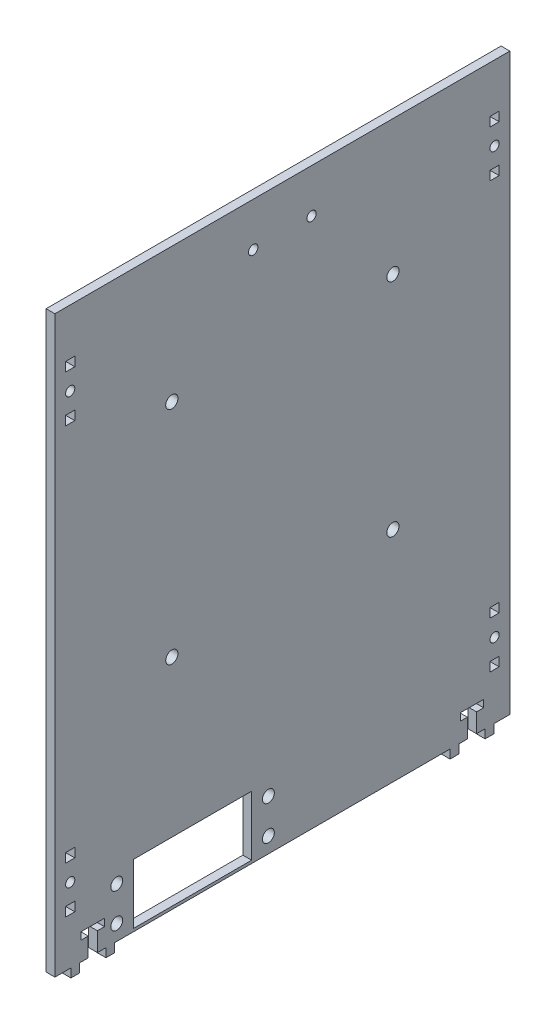
SolidWorks part; units mm, degrees
ref_plane "Front Plane" through (0, 0, 0) normal (0, 0, 1) x (1, 0, 0)
ref_plane "Top Plane" through (0, 0, 0) normal (0, 1, 0) x (1, 0, 0)
ref_plane "Right Plane" through (0, 0, 0) normal (1, 0, 0) x (0, 0, -1)
sketch "Sketch1" plane through (0, 0, 0) normal (1, 0, 0) x (0, 0, -1)
  line L0 (11.425, 0) -> (8.5, 0)
  line L1 (135.5, -3) -> (135.5, 0)
  line L2 (67.45, 21.5) -> (26.95, 21.5)
  line L3 (26.95, 21.5) -> (26.95, 1)
  line L4 (67.45, 21.5) -> (67.45, 1)
  line L5 (26.95, 1) -> (67.45, 1)
  line L6 (8.5, 0) -> (8.5, -3)
  line L7 (8.5, -3) -> (5.5, -3)
  line L8 (0, 0) -> (0, 197)
  line L9 (5.5, -3) -> (5.5, 0)
  line L10 (11.425, 0) -> (11.425, 6.5)
  line L11 (11.425, 6.5) -> (9, 6.5)
  line L12 (9, 6.5) -> (9, 9)
  line L13 (9, 9) -> (17, 9)
  line L14 (17, 9) -> (17, 6.5)
  line L15 (17, 6.5) -> (14.575, 6.5)
  line L16 (14.575, 6.5) -> (14.575, 0)
  line L17 (-1000, 98.5) -> (49000, 98.5) construction
  line L18 (3.675, 16) -> (6.825, 16)
  line L19 (3.675, 16) -> (3.675, 19.15)
  line L20 (3.675, 19.15) -> (6.825, 19.15)
  line L21 (6.825, 16) -> (6.825, 19.15)
  line L22 (3.675, 16) -> (6.825, 19.15) construction
  line L23 (3.675, 19.15) -> (6.825, 16) construction
  line L24 (3.675, 32) -> (6.825, 32)
  line L25 (3.675, 32) -> (3.675, 35.15)
  line L26 (3.675, 35.15) -> (6.825, 35.15)
  line L27 (6.825, 32) -> (6.825, 35.15)
  line L28 (3.675, 32) -> (6.825, 35.15) construction
  line L29 (3.675, 35.15) -> (6.825, 32) construction
  line L30 (14.575, 0) -> (17.5, 0)
  line L31 (78, -1000) -> (78, 49000) construction
  line L32 (3.675, 161.85) -> (6.825, 165) construction
  line L33 (3.675, 165) -> (6.825, 161.85) construction
  line L34 (3.675, 177.85) -> (6.825, 181) construction
  line L35 (3.675, 181) -> (6.825, 177.85) construction
  line L36 (0, 197) -> (156, 197)
  line L37 (6.825, 165) -> (6.825, 161.85)
  line L38 (3.675, 161.85) -> (6.825, 161.85)
  line L39 (3.675, 165) -> (3.675, 161.85)
  line L40 (3.675, 165) -> (6.825, 165)
  line L41 (6.825, 181) -> (6.825, 177.85)
  line L42 (3.675, 177.85) -> (6.825, 177.85)
  line L43 (3.675, 181) -> (3.675, 177.85)
  line L44 (3.675, 181) -> (6.825, 181)
  line L45 (5.5, 0) -> (0, 0)
  line L46 (17.5, 0) -> (17.5, -3)
  line L47 (17.5, -3) -> (20.5, -3)
  line L48 (20.5, -3) -> (20.5, 0)
  line L49 (20.5, 0) -> (135.5, 0)
  line L50 (138.5, -3) -> (135.5, -3)
  line L51 (138.5, 0) -> (138.5, -3)
  line L52 (141.425, 0) -> (138.5, 0)
  line L53 (144.575, 0) -> (147.5, 0)
  line L54 (150.5, 0) -> (156, 0)
  line L55 (150.5, -3) -> (150.5, 0)
  line L56 (147.5, -3) -> (150.5, -3)
  line L57 (147.5, 0) -> (147.5, -3)
  line L58 (37, 71.9) -> (37, 153.9) construction
  line L59 (37, 153.9) -> (119, 153.9) construction
  line L60 (119, 153.9) -> (119, 71.9) construction
  line L61 (152.325, 181) -> (149.175, 177.85) construction
  line L62 (152.325, 177.85) -> (149.175, 181) construction
  line L63 (152.325, 165) -> (149.175, 161.85) construction
  line L64 (152.325, 161.85) -> (149.175, 165) construction
  line L65 (152.325, 35.15) -> (149.175, 32) construction
  line L66 (152.325, 32) -> (149.175, 35.15) construction
  line L67 (152.325, 19.15) -> (149.175, 16) construction
  line L68 (152.325, 16) -> (149.175, 19.15) construction
  line L69 (119, 71.9) -> (37, 71.9) construction
  line L70 (88, 182) -> (68, 182) construction
  line L85 (152.325, 181) -> (149.175, 181)
  line L86 (152.325, 181) -> (152.325, 177.85)
  line L87 (152.325, 177.85) -> (149.175, 177.85)
  line L88 (149.175, 181) -> (149.175, 177.85)
  line L89 (152.325, 165) -> (149.175, 165)
  line L90 (152.325, 165) -> (152.325, 161.85)
  line L91 (152.325, 161.85) -> (149.175, 161.85)
  line L92 (149.175, 165) -> (149.175, 161.85)
  line L93 (149.175, 32) -> (149.175, 35.15)
  line L94 (152.325, 35.15) -> (149.175, 35.15)
  line L95 (152.325, 32) -> (152.325, 35.15)
  line L96 (152.325, 32) -> (149.175, 32)
  line L97 (149.175, 16) -> (149.175, 19.15)
  line L98 (152.325, 19.15) -> (149.175, 19.15)
  line L99 (152.325, 16) -> (152.325, 19.15)
  line L100 (152.325, 16) -> (149.175, 16)
  line L101 (141.425, 6.5) -> (141.425, 0)
  line L102 (139, 6.5) -> (141.425, 6.5)
  line L103 (139, 9) -> (139, 6.5)
  line L104 (147, 9) -> (139, 9)
  line L105 (147, 6.5) -> (147, 9)
  line L106 (144.575, 6.5) -> (147, 6.5)
  line L107 (144.575, 0) -> (144.575, 6.5)
  line L109 (156, 0) -> (156, 197)
  circle A0 centre (5.25, 25.575) radius 1.575
  circle A1 centre (5.25, 171.425) radius 1.575
  circle A2 centre (150.75, 171.425) radius 1.575
  circle A3 centre (150.75, 25.575) radius 1.575
  circle A4 centre (73.2, 5.35) radius 2.05
  circle A5 centre (73.2, 17.15) radius 2.05
  circle A6 centre (21.2, 5.35) radius 2.05
  circle A7 centre (21.2, 17.15) radius 2.05
  circle A8 centre (40.1, 75) radius 2.1
  circle A9 centre (40.1, 150.8) radius 2.1
  circle A10 centre (115.9, 75) radius 2.1
  circle A11 centre (115.9, 150.8) radius 2.1
  circle A12 centre (88, 182) radius 1.6
  circle A13 centre (68, 182) radius 1.6
  point P3 (13, 9)
  point P4 (143, 9)
  point P16 (5.25, 17.575)
  point P29 (5.25, 33.575)
  point P58 (0, 98.5)
  point P65 (5.25, 163.425)
  point P66 (5.25, 179.425)
  point P88 (78, 0)
  point P98 (78, 153.9)
  point P104 (78, 197)
  point P105 (78, 0)
  point P114 (78, 182)
  point P121 (150.75, 179.425)
  point P122 (150.75, 163.425)
  point P123 (156, 98.5)
  point P124 (150.75, 33.575)
  point P125 (150.75, 17.575)
  dimension "D19" = 3.15
  dimension "D23" = 20.5
  dimension "D24" = 4.1
  dimension "D25" = 4.1
  dimension "D30" = 4.1
  dimension "D31" = 4.1
  dimension "D44" = 4.2
  dimension "D50" = 4.2
  dimension "D52" = 3.2
  dimension "D55" = 3.2
  dimension "D3" = 130
  dimension "D4" = 156
  dimension "D5" = 5.25
  dimension "D6" = 4.5
  dimension "D7" = 4.5
  dimension "D8" = 2.5
  dimension "D9" = 98.5
  dimension "D10" = 2.5
  dimension "D11" = 8
  dimension "D12" = 8
  dimension "D13" = 8
  dimension "D14" = 3.15
  dimension "D15" = 2.425
  dimension "D16" = 3.15
  dimension "D17" = 3.15
  dimension "D18" = 5.75
  dimension "D20" = 5.75
  dimension "D21" = 3.15
  dimension "D22" = 3.15
  dimension "D26" = 4.35
  dimension "D27" = 4.35
  dimension "D28" = 3
  dimension "D29" = 5.75
  dimension "D32" = 5.75
  dimension "D33" = 4.35
  dimension "D34" = 4.35
  dimension "D35" = 9.95
  dimension "D36" = 40.5
  dimension "D37" = 11.8
  dimension "D38" = 3
  dimension "D39" = 3
  dimension "D40" = 3
  dimension "D41" = 9
  dimension "D42" = 17.575
  dimension "D43" = 1
  dimension "D45" = 75
  dimension "D46" = 82
  dimension "D47" = 82
  dimension "D48" = 3.1
  dimension "D49" = 3.1
  dimension "D51" = 3.1
  dimension "D53" = 15
  dimension "D54" = 20
extrude "Boss-Extrude2" add sketch "Sketch1" along normal blind 1.5 and the other way blind 1.5
